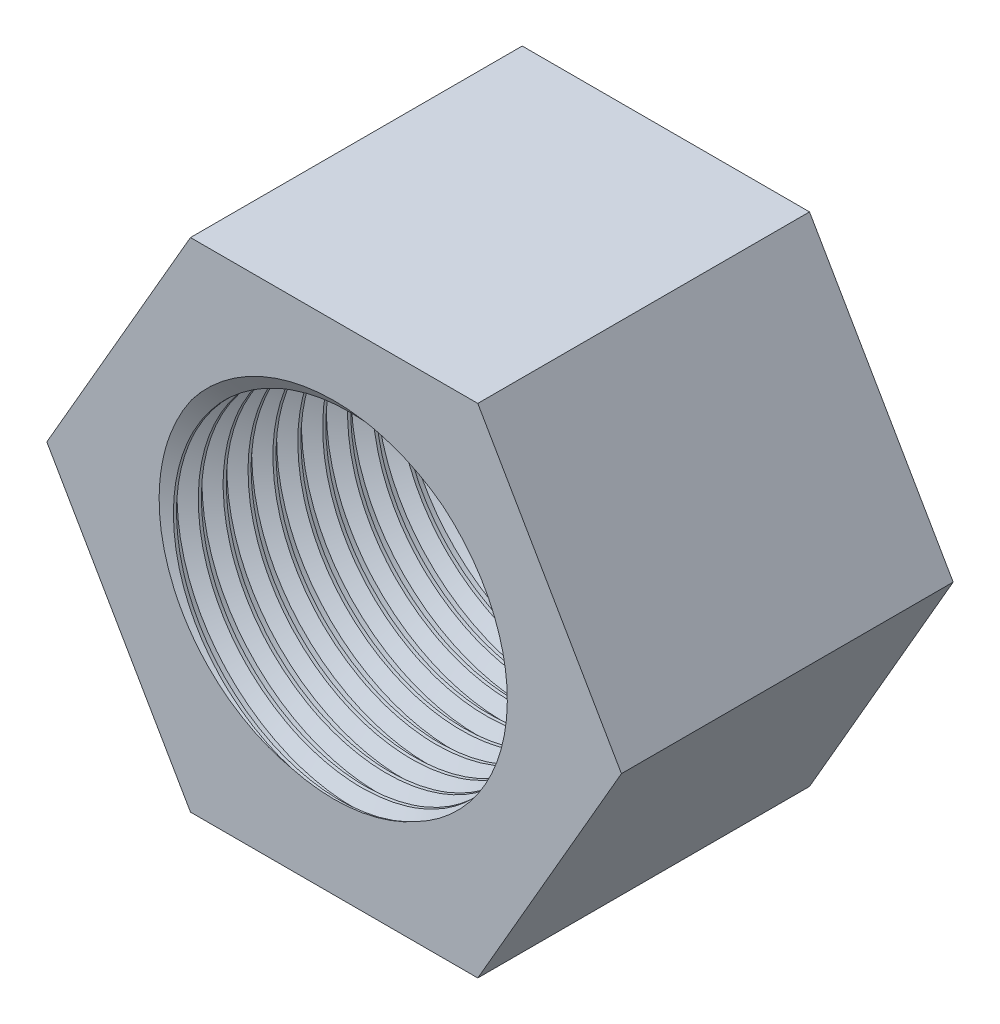
SolidWorks part; units mm, degrees
material "Ductile Iron"
ref_plane "Front Plane" through (0, 0, 0) normal (0, 0, 1) x (1, 0, 0)
ref_plane "Top Plane" through (0, 0, 0) normal (0, 1, 0) x (1, 0, 0)
ref_plane "Right Plane" through (0, 0, 0) normal (1, 0, 0) x (0, 0, -1)
sketch "Sketch1" plane through (0, 0, 0) normal (0, 0, 1) x (1, 0, 0)
  line L1 (-17.3205, 0) -> (-8.6603, -15)
  line L2 (-8.6603, -15) -> (8.6603, -15)
  line L3 (8.6603, -15) -> (17.3205, 0)
  line L4 (17.3205, 0) -> (8.6603, 15)
  line L5 (8.6603, 15) -> (-8.6603, 15)
  line L6 (-8.6603, 15) -> (-17.3205, 0)
  circle A0 centre (0, 0) radius 15 construction
  circle A1 centre (0, 0) radius 10
  dimension "D2" = 20
  dimension "D1" = 30
extrude "Boss-Extrude1" add sketch "Sketch1" along normal blind 20
thread "Thread1" pitch 1.5 method cut profile "Thread Profile1" start angle 0, offset 10, length 30, pitch 1.5, diameter 20
ref_plane "Plane1" through (-10, 0, 30) normal (0, 1, 0) x (1, 0, 0)
sketch "Thread Profile1" plane through (-10, 0, 30) normal (0, 1, 0) x (1, 0, 0)
  line L0 (0, 0) -> (0, 1.5) construction
  line L11 (0, 0) -> (0, 1.3125)
  line L12 (0, 1.3125) -> (-0.8119, 0.8437)
  line L13 (-0.8119, 0.8437) -> (-0.8119, 0.4687)
  line L15 (-0.8119, 0.4687) -> (0, 0)
  line L17 (-0.8119, 0.6562) -> (0, 0.6562) construction
  point P2 (0, 0)
  dimension "Pitch" = 1.5
  dimension "Profile_Angle" = 60
  dimension "Profile_Land" = 0.375
  dimension "Profile_Height" = 0.8119
